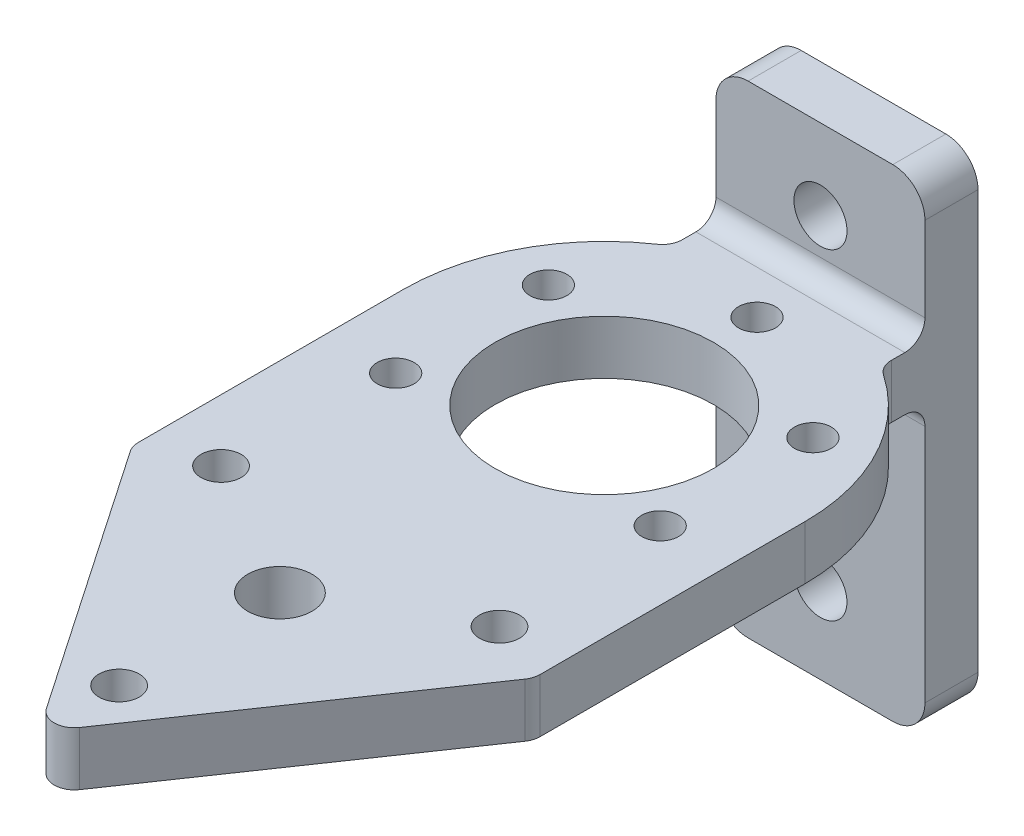
SolidWorks part; units mm, degrees
material "PLA"
ref_plane "Plan de face" through (0, 0, 0) normal (0, 0, 1) x (1, 0, 0)
ref_plane "Plan de dessus" through (0, 0, 0) normal (0, 1, 0) x (1, 0, 0)
ref_plane "Plan de droite" through (0, 0, 0) normal (1, 0, 0) x (0, 0, -1)
sketch "Esquisse1" plane through (0, 0, 0) normal (0, 0, 1) x (1, 0, 0)
  line L0 (55, 0) -> (-55, 0) construction
  line L1 (-6.5, -15) -> (6.5, -15)
  line L2 (-6.5, -15) -> (-6.5, 15)
  line L3 (-6.5, 15) -> (6.5, 15)
  line L4 (6.5, -15) -> (6.5, 15)
  line L5 (-6.5, -15) -> (6.5, 15) construction
  line L6 (-6.5, 15) -> (6.5, -15) construction
  circle A0 centre (0, 10) radius 1.65
  circle A1 centre (0, -10) radius 1.65
  point P0 (0, 0)
  dimension "D4" = 3.3
  dimension "D1" = 30
  dimension "D2" = 13
  dimension "D3" = 10
extrude "Boss.-Extru.1" add sketch "Esquisse1" along normal blind 3.3
fillet "Congé1" radius 2 4 edges at (6.5, -15, 1.65) (-6.5, -15, 1.65) (6.5, 15, 1.65) (-6.5, 15, 1.65)
sketch "Esquisse2" plane through (0, 0, 3.3) normal (0, 0, 1) x (1, 0, 0)
  line L0 (6.5, -13) -> (6.5, 13) construction
  line L3 (-6.5, 6.5) -> (6.5, 6.5)
  line L5 (-6.5, 13) -> (-6.5, -13) construction
  line L7 (-6.5, 6.5) -> (-6.5, 3.15)
  line L10 (-6.5, 3.15) -> (6.5, 3.15)
  line L14 (6.5, 6.5) -> (6.5, 3.15)
  point P0 (0, 0)
  point P8 (0, 0)
  dimension "D1" = 3.15
  dimension "D3" = 3.35
extrude "Boss.-Extru.2" add sketch "Esquisse2" along normal blind 2.77
sketch "Esquisse4" plane through (0, 6.5, 0) normal (0, 1, 0) x (1, 0, 0)
  line L1 (-6.5, -6.07) -> (6.5, -6.07)
  line L3 (-6.5, -27.4242) -> (6.5, -27.4242)
  circle A4 centre (0, -16.7471) radius 6.8
  arc A5 (-6.5, -6.07) -> (-6.5, -27.4242) centre (0, -16.7471) ccw
  arc A6 (6.5, -27.4242) -> (6.5, -6.07) centre (0, -16.7471) ccw
  point P25 (0, -16.7471)
  point P28 (0, -16.7471)
  dimension "D2" = 12.5
  dimension "D3" = 13
  dimension "D6" = 13.6
  dimension "D1" = 12.5
extrude "Boss.-Extru.4" add sketch "Esquisse4" against normal up to surface (3.35 mm away) up to face at (0, 3.15, 4.685)
sketch "Esquisse6" plane through (0, 6.5, 0) normal (0, 1, 0) x (1, 0, 0)
  line L2 (0, -16.7471) -> (8.2272, -11.9971) construction
  line L3 (0, -16.7471) -> (-8.2272, -11.9971) construction
  line L4 (0, -16.7471) -> (0, -7.2471) construction
  line L5 (0, -16.7471) -> (-8.2272, -21.4971) construction
  line L6 (0, -16.7471) -> (0, -26.2471) construction
  line L7 (0, -16.7471) -> (8.2272, -21.4971) construction
  circle A0 centre (0, -7.2471) radius 1.15
  circle A1 centre (-8.2272, -11.9971) radius 1.15
  circle A2 centre (8.2272, -11.9971) radius 1.15
  circle A3 centre (-8.2272, -21.4971) radius 1.15
  circle A7 centre (8.2272, -21.4971) radius 1.15
  dimension "D2" = 2.3
  dimension "D5" = 2.3
  dimension "D6" = 2.3
  dimension "D7" = 9.5
  dimension "D14" = 2.3
  dimension "D15" = 2.3
  dimension "D1" = 9.5
  dimension "D3" = 60
  dimension "D4" = 60
  dimension "D8" = 9.5
  dimension "D9" = 60
  dimension "D10" = 60
  dimension "D11" = 9.5
  dimension "D12" = 9.5
  dimension "D13" = 9.5
extrude "Enlèv. mat.-Extru.2" cut sketch "Esquisse6" against normal through all
sketch "Esquisse8" plane through (0, 6.5, 0) normal (0, 1, 0) x (1, 0, 0)
  line L6 (-6.5, -27.4242) -> (6.5, -27.4242) construction
  line L8 (0, -9.9471) -> (0, -23.5471) construction
  line L9 (0, -36.9271) -> (0, -27.4242) construction
  line L10 (0, -36.9271) -> (8.6603, -31.9271) construction
  line L11 (0, -36.9271) -> (-8.6603, -31.9271) construction
  line L16 (12.5, -16.7471) -> (12.5, -33.6271) construction
  line L17 (-12.5, -16.7471) -> (-12.5, -33.6258) construction
  line L18 (0, -51.9271) -> (-12.5, -33.6258)
  line L19 (-12.5, -33.6258) -> (-12.5, -16.7471)
  line L20 (0, -51.9271) -> (12.5, -33.6271)
  line L21 (12.5, -33.6271) -> (12.5, -16.7471)
  line L22 (-6.5, -27.4242) -> (6.5, -27.4242)
  circle A0 centre (0, -36.9271) radius 2
  circle A1 centre (0, -36.9271) radius 10 construction
  circle A2 centre (8.6603, -31.9271) radius 1.25
  circle A3 centre (0, -16.7471) radius 6.8 construction
  circle A4 centre (-8.6603, -31.9271) radius 1.25
  circle A7 centre (0, -46.9271) radius 1.25
  arc A8 (6.5, -27.4242) -> (6.5, -6.07) centre (0, -16.7471) ccw construction
  arc A9 (-6.5, -6.07) -> (-6.5, -27.4242) centre (0, -16.7471) ccw construction
  arc A11 (-12.5, -16.7471) -> (-6.5, -27.4242) centre (0, -16.7471) ccw
  arc A12 (12.5, -16.7471) -> (6.5, -27.4242) centre (0, -16.7471) cw
  point P16 (0, -16.7471)
  dimension "D2" = 4
  dimension "D5" = 2.5
  dimension "D6" = 2.5
  dimension "D7" = 2.5
  dimension "D1" = 20.18
  dimension "D3" = 120
  dimension "D4" = 60
  dimension "D8" = 16.8787
  dimension "D9" = 16.88
  dimension "D10" = 5
  dimension "D11" = 8.6603
extrude "Boss.-Extru.5" add sketch "Esquisse8" against normal up to surface (3.35 mm away) up to face at (0, 3.15, 8.3971)
fillet "Congé2" radius 1.25 7 edges at (12.5, 4.825, 33.6271) (-12.5, 4.825, 33.6258) (0, 4.825, 51.9271) (0, 3.15, 3.3) (0, 6.5, 3.3) (6.5, 4.825, 6.07) (-6.5, 4.825, 6.07)
